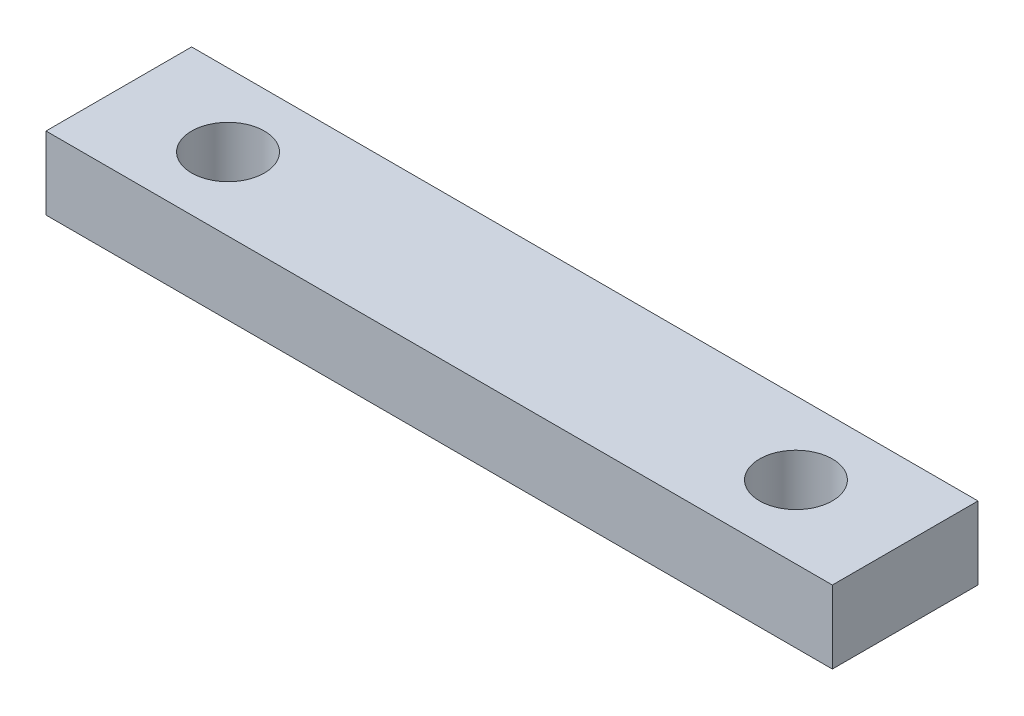
SolidWorks part; units mm, degrees
ref_plane "Front Plane" through (0, 0, 0) normal (0, 0, 1) x (1, 0, 0)
ref_plane "Top Plane" through (0, 0, 0) normal (0, 1, 0) x (1, 0, 0)
ref_plane "Right Plane" through (0, 0, 0) normal (1, 0, 0) x (0, 0, -1)
sketch "Sketch1" plane through (0, 0, 0) normal (0, 1, 0) x (1, 0, 0)
  line L0 (-27, 0) -> (-19.5, 0) construction
  line L1 (-27, 5) -> (27, 5)
  line L2 (-27, 5) -> (-27, -5)
  line L3 (-27, -5) -> (27, -5)
  line L4 (27, 5) -> (27, -5)
  line L5 (-27, 5) -> (27, -5) construction
  line L6 (-27, -5) -> (27, 5) construction
  line L7 (-19.5, 0) -> (19.5, 0) construction
  circle A0 centre (-19.5, 0) radius 2.5
  circle A1 centre (19.5, 0) radius 2.5
  point P0 (0, 0)
  dimension "D5" = 5
  dimension "D7" = 5
  dimension "D1" = 54
  dimension "D2" = 10
  dimension "D3" = 7.5
  dimension "D4" = 5
  dimension "D6" = 39
extrude "Boss-Extrude1" add sketch "Sketch1" along normal blind 2.5 and the other way blind 2.5
